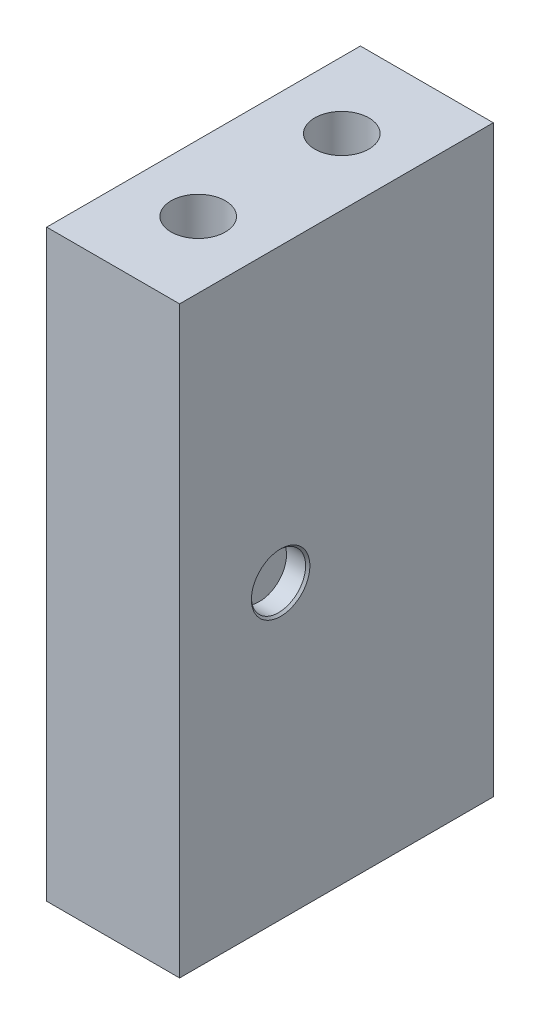
SolidWorks part; units mm, degrees
material "ABS"
ref_plane "Front Plane" through (0, 0, 0) normal (0, 0, 1) x (1, 0, 0)
ref_plane "Top Plane" through (0, 0, 0) normal (0, 1, 0) x (1, 0, 0)
ref_plane "Right Plane" through (0, 0, 0) normal (1, 0, 0) x (0, 0, -1)
sketch "Sketch1" plane through (0, 0, 0) normal (0, 1, 0) x (1, 0, 0)
  line L0 (0, 0) -> (6.25, 0) construction
  line L1 (6.25, -14.75) -> (-6.25, -14.75)
  line L2 (6.25, -14.75) -> (6.25, 14.75)
  line L3 (6.25, 14.75) -> (-6.25, 14.75)
  line L4 (-6.25, -14.75) -> (-6.25, 14.75)
  line L5 (6.25, -14.75) -> (-6.25, 14.75) construction
  line L6 (6.25, 14.75) -> (-6.25, -14.75) construction
  line L7 (-6.25, -14.75) -> (-6.25, 14.75) construction
  line L8 (-6.25, -14.75) -> (-6.25, 14.75) construction
  circle A0 centre (0, 6.75) radius 2.55
  circle A1 centre (0, -6.75) radius 2.55
  point P0 (0, 0)
  dimension "D4" = 5.1
  dimension "D1" = 12.5
  dimension "D3" = 8
extrude "Boss-Extrude1" add sketch "Sketch1" along normal mid plane 54.9
sketch "Sketch2" plane through (6.25, 0, 0) normal (1, 0, 0) x (0, 0, -1)
  line L2 (14.75, 27.45) -> (14.75, -27.45) construction
  circle A0 centre (-5.25, 0) radius 2.55
  dimension "D1" = 5.1
  dimension "D2" = 20
extrude "Cut-Extrude1" cut sketch "Sketch2" against normal blind 2
chamfer "Chamfer1" distance 0.2 angle 45 1 edges at (6.25, 0, 2.7)
